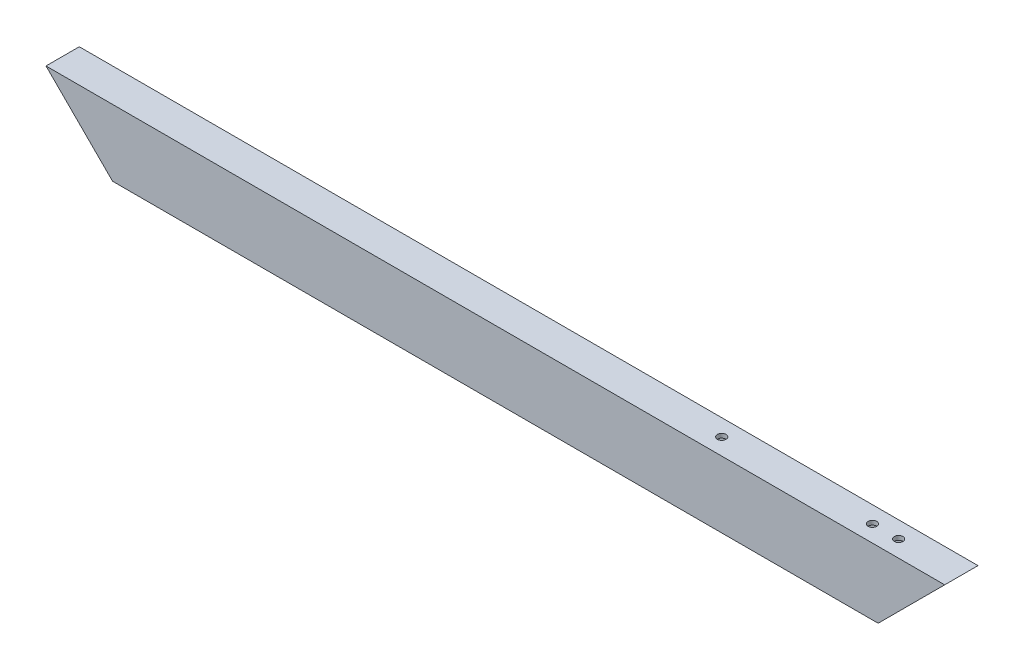
SolidWorks part; units mm, degrees
ref_plane "Front Plane" through (0, 0, 0) normal (0, 0, 1) x (1, 0, 0)
ref_plane "Top Plane" through (0, 0, 0) normal (0, 1, 0) x (1, 0, 0)
ref_plane "Right Plane" through (0, 0, 0) normal (1, 0, 0) x (0, 0, -1)
sketch "Sketch1" plane through (0, 0, 0) normal (1, 0, 0) x (0, 0, -1)
  line L1 (-9.525, -22.225) -> (9.525, -22.225)
  line L2 (-9.525, -22.225) -> (-9.525, 22.225)
  line L3 (-9.525, 22.225) -> (9.525, 22.225)
  line L4 (9.525, -22.225) -> (9.525, 22.225)
  line L5 (-9.525, -22.225) -> (9.525, 22.225) construction
  line L6 (-9.525, 22.225) -> (9.525, -22.225) construction
  line L7 (-12.7, -25.4) -> (12.7, -25.4)
  line L8 (-12.7, -25.4) -> (-12.7, 25.4)
  line L9 (-12.7, 25.4) -> (12.7, 25.4)
  line L10 (12.7, -25.4) -> (12.7, 25.4)
  line L11 (-12.7, -25.4) -> (12.7, 25.4) construction
  line L12 (-12.7, 25.4) -> (12.7, -25.4) construction
  point P0 (0, 0)
  point P6 (0, 0)
  dimension "D1" = 25.4
  dimension "D2" = 50.8
  dimension "D3" = 3.175
  dimension "D4" = 3.175
extrude "Boss-Extrude1" add sketch "Sketch1" along normal mid plane 685.8
sketch "Sketch2" plane through (0, 0, -12.7) normal (0, 0, -1) x (-1, 0, 0)
  line L0 (342.9, 25.4) -> (292.1, -25.4)
  line L1 (-342.9, -25.4) -> (342.9, -25.4) construction
  line L2 (-342.9, 25.4) -> (342.9, 25.4) construction
  line L3 (0, 13.97) -> (0, -13.97) construction
  line L4 (-342.9, 25.4) -> (-292.1, -25.4)
  line M2 (342.9, -25.4) -> (342.9, 25.4)
  line M4 (-342.9, 25.4) -> (-342.9, -25.4)
  line M5 (-342.9, -25.4) -> (342.9, -25.4)
  dimension "D1" = 45
extrude "Cut-Extrude1" cut sketch "Sketch2" against normal through all and the other way through all contours L0 M2 M5 | L4 M4 M5 region at (-325.9667, -8.4667, -12.7) region at (325.9667, -8.4667, -12.7)
sketch "Sketch3" plane through (0, 0, -12.7) normal (0, 0, -1) x (-1, 0, 0)
  line L0 (-292.1, -25.4) -> (292.1, -25.4) construction
  circle A0 centre (-241.3, 0) radius 11.1125
  circle A1 centre (-190.5, 0) radius 11.1125
  dimension "D1" = 22.225
  dimension "D4" = 101.6
  dimension "D5" = 50.8
  dimension "D2" = 25.4
  dimension "D3" = 2
extrude "Cut-Extrude2" cut sketch "Sketch3" against normal up to next
hole_wizard "M6 Clearance Hole1" positions "Sketch5" profile "Sketch6" hole size "M6" standard "ANSI Metric" end condition up to next
sketch "Sketch5" plane through (0, 25.4, 0) normal (0, 1, 0) x (1, 0, 0)
  point P0 (295.0286, 0)
  point P3 (275.0286, 0)
  point P6 (160.0286, 0)
sketch "Sketch6" plane through (295.0286, 25.4, 0) normal (1, 0, 0) x (0, 0, 1)
  line L0 (0, 0) -> (0, 3.175)
  line L1 (0, 3.175) -> (3.3, 3.175)
  line L2 (3.3, 3.175) -> (3.3, 0)
  line L5 (3.3, 0) -> (0, 0)
  line L11 (0, -6.35) -> (0, 107.95) construction
  dimension "Thru Hole Dia." = 6.6
  dimension "Thru Hole Depth" = 3.175
